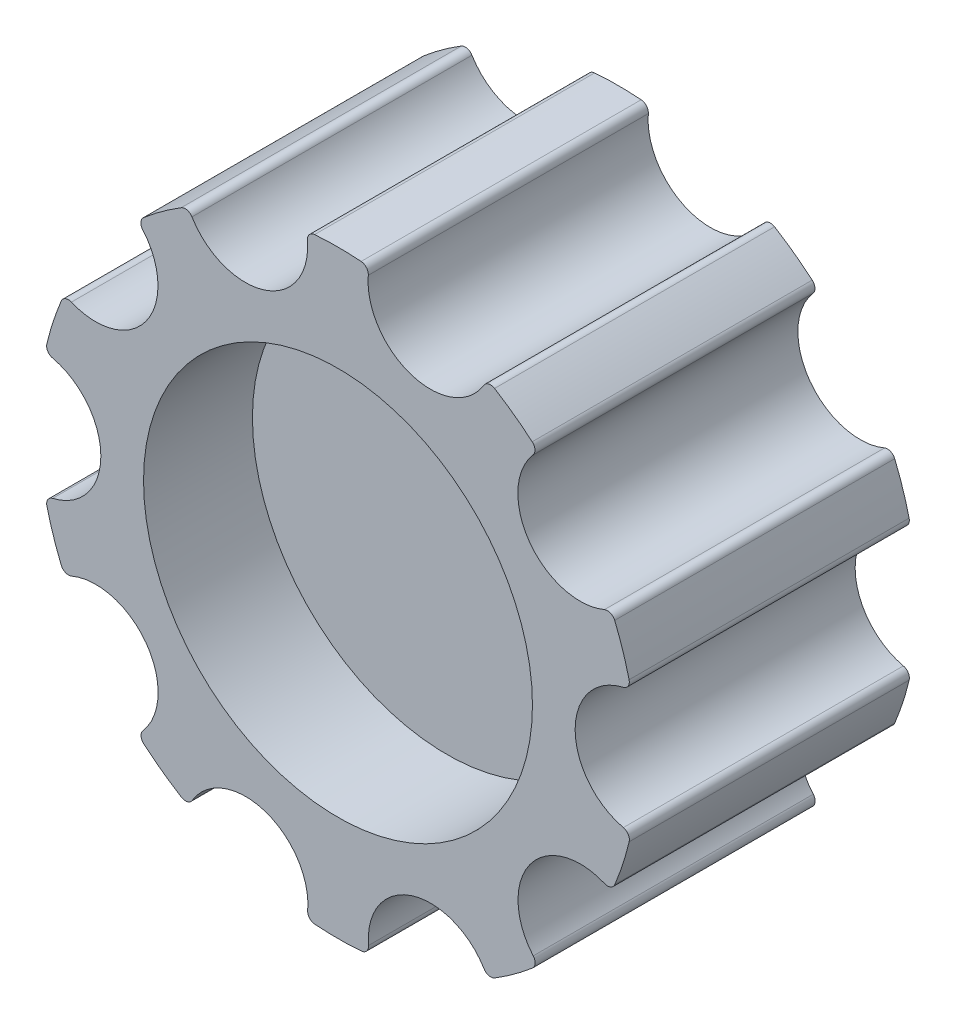
SolidWorks part; units mm, degrees
ref_plane "Front Plane" through (0, 0, 0) normal (0, 0, 1) x (1, 0, 0)
ref_plane "Top Plane" through (0, 0, 0) normal (0, 1, 0) x (1, 0, 0)
ref_plane "Right Plane" through (0, 0, 0) normal (1, 0, 0) x (0, 0, -1)
sketch "Sprocket" plane through (-521.3339, -864.335, -1401.844) normal (0, 0, 1) x (1, 0, 0)
  arc A8 (502.6212, 859.8188) -> (503.5468, 856.9742) centre (521.3339, 864.335) ccw
  arc A9 (502.9935, 860.4231) -> (502.6212, 859.8188) centre (503.1072, 859.9362) ccw
  arc A10 (503.5468, 856.9742) -> (504.2034, 856.7048) centre (504.0088, 857.1653) ccw
  arc A11 (504.1968, 871.9504) -> (503.5404, 871.6804) centre (504.0026, 871.4896) ccw
  arc A12 (503.5404, 871.6804) -> (502.6172, 868.8349) centre (521.3339, 864.335) ccw
  arc A13 (502.6172, 868.8349) -> (502.9901, 868.2311) centre (503.1034, 868.7181) ccw
  arc A14 (511.9459, 880.5689) -> (511.2562, 880.7363) centre (511.518, 880.3103) ccw
  arc A15 (511.2562, 880.7363) -> (508.8368, 878.9769) centre (521.3339, 864.335) ccw
  arc A16 (508.8368, 878.9769) -> (508.7835, 878.2692) centre (509.1614, 878.5966) ccw
  arc A17 (523.2809, 882.9866) -> (522.8213, 883.5275) centre (522.7827, 883.029) ccw
  arc A18 (522.8213, 883.5275) -> (519.8298, 883.5262) centre (521.3339, 864.335) ccw
  arc A19 (519.8298, 883.5262) -> (519.3707, 882.9849) centre (519.8689, 883.0277) ccw
  arc A20 (533.8722, 878.2801) -> (533.8183, 878.9877) centre (533.494, 878.6072) ccw
  arc A21 (533.8183, 878.9877) -> (531.3973, 880.7451) centre (521.3339, 864.335) ccw
  arc A22 (531.3973, 880.7451) -> (530.7078, 880.577) centre (531.136, 880.3188) ccw
  arc A23 (539.6743, 868.247) -> (540.0466, 868.8512) centre (539.5606, 868.7339) ccw
  arc A24 (540.0466, 868.8512) -> (539.121, 871.6959) centre (521.3339, 864.335) ccw
  arc A25 (539.121, 871.6959) -> (538.4644, 871.9653) centre (538.659, 871.5047) ccw
  arc A26 (538.471, 856.7196) -> (539.1274, 856.9896) centre (538.6652, 857.1804) ccw
  arc A27 (539.1274, 856.9896) -> (540.0506, 859.8351) centre (521.3339, 864.335) ccw
  arc A28 (540.0506, 859.8351) -> (539.6777, 860.439) centre (539.5644, 859.952) ccw
  arc A29 (530.7219, 848.1011) -> (531.4116, 847.9337) centre (531.1498, 848.3597) ccw
  arc A30 (531.4116, 847.9337) -> (533.831, 849.6931) centre (521.3339, 864.335) ccw
  arc A31 (533.831, 849.6931) -> (533.8843, 850.4008) centre (533.5064, 850.0734) ccw
  arc A32 (519.3869, 845.6834) -> (519.8465, 845.1426) centre (519.8851, 845.6411) ccw
  arc A33 (519.8465, 845.1426) -> (522.838, 845.1439) centre (521.3339, 864.335) ccw
  arc A34 (522.838, 845.1439) -> (523.2971, 845.6851) centre (522.7989, 845.6423) ccw
  arc A35 (508.7956, 850.39) -> (508.8495, 849.6823) centre (509.1738, 850.0629) ccw
  arc A36 (508.8495, 849.6823) -> (511.2705, 847.925) centre (521.3339, 864.335) ccw
  arc A37 (511.2705, 847.925) -> (511.96, 848.093) centre (511.5318, 848.3512) ccw
  arc A38 (504.1968, 871.9504) -> (508.7835, 878.2692) centre (505.7538, 875.6443) ccw
  arc A39 (502.9901, 868.2311) -> (502.9935, 860.4231) centre (502.0819, 864.3267) cw
  arc A40 (504.2034, 856.7048) -> (508.7956, 850.39) centre (505.7636, 853.0122) cw
  arc A41 (511.96, 848.093) -> (519.3869, 845.6834) centre (515.3927, 846.0227) cw
  arc A42 (530.7219, 848.1011) -> (523.2971, 845.6851) centre (527.291, 846.0279) ccw
  arc A43 (538.471, 856.7196) -> (533.8843, 850.4008) centre (536.914, 853.0258) ccw
  arc A44 (539.6743, 868.247) -> (539.6777, 860.439) centre (540.5859, 864.3434) ccw
  arc A45 (533.8722, 878.2801) -> (538.4644, 871.9653) centre (536.9041, 875.6578) ccw
  arc A46 (523.2809, 882.9866) -> (530.7078, 880.577) centre (527.2751, 882.6473) ccw
  arc A47 (511.9459, 880.5689) -> (519.3707, 882.9849) centre (515.3768, 882.6421) ccw
  dimension "D3" = 38.5
  dimension "D4" = 1
  dimension "D5" = 1
extrude "Sproket" add sketch "Sprocket" along normal blind 9 contours A44 A28 A27 A26 A43 A31 A30 A29 A42 A34 A33 A32 A41 A37 A36 A35 A40 A10 A8 A9 A39 A13 A12 A11 A38 A16 A15 A14 A47 A19 A18 A17 A46 A22 A21 A20 A45 A25 A24 A23
sketch "Sketch3" plane through (0, 0, -1392.844) normal (0, 0, 1) x (1, 0, 0)
  circle A0 centre (0, 0) radius 12.5
  dimension "D1" = 25
extrude "Cut-Extrude1" cut sketch "Sketch3" against normal blind 7
mirror "Mirror1" about plane through (9.1133, 2.1994, -1401.844) normal (0, 0, 1) of "Sproket", "Cut-Extrude1"
ref_axis "Wheel_Axis" through (0, 0, -1413.4135) along (0, 0, 1)
sketch "Sketch4" plane through (0, 0, -1403.844) normal (0, 0, -1) x (-1, 0, 0)
  line L0 (-1.3038, 1.45) -> (1.3038, 1.45)
  circle A0 centre (0, 0) radius 4.5
  arc A1 (-1.3038, 1.45) -> (1.3038, 1.45) centre (0, 0) ccw
  dimension "D1" = 9
  dimension "D2" = 3.9
  dimension "D3" = 1.45
extrude "Boss-Extrude1" add sketch "Sketch4" along normal blind 7
